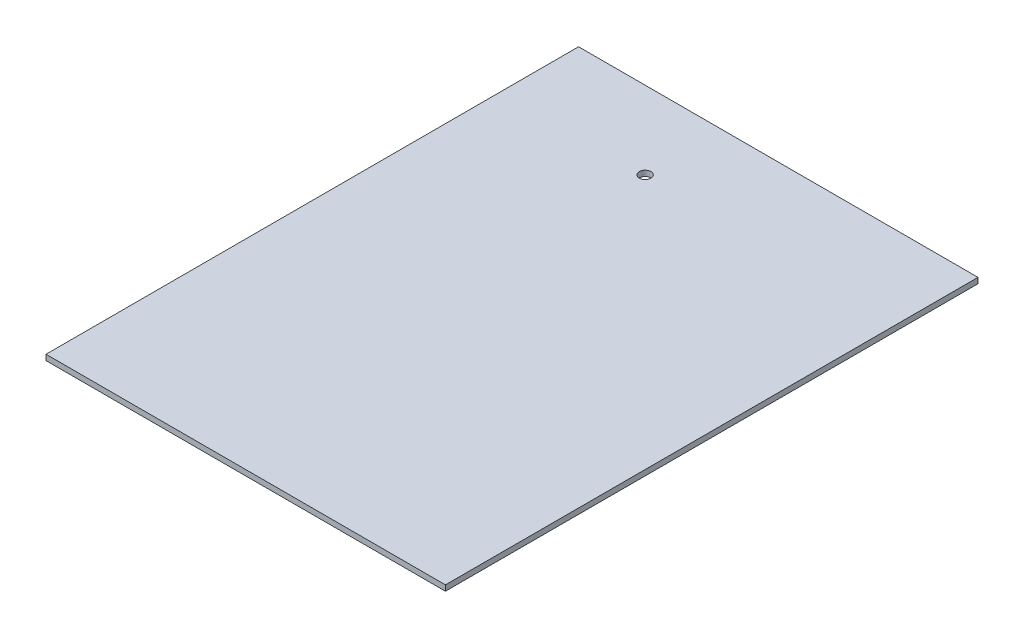
SolidWorks part; units mm, degrees
ref_plane "Front Plane" through (0, 0, 0) normal (0, 0, 1) x (1, 0, 0)
ref_plane "Top Plane" through (0, 0, 0) normal (0, 1, 0) x (1, 0, 0)
ref_plane "Right Plane" through (0, 0, 0) normal (1, 0, 0) x (0, 0, -1)
sketch "Sketch1" plane through (0, 0, 0) normal (0, 1, 0) x (1, 0, 0)
  line L1 (0, 0) -> (-457.2, 0)
  line L2 (0, 0) -> (0, 609.6)
  line L3 (0, 609.6) -> (-457.2, 609.6)
  line L4 (-457.2, 0) -> (-457.2, 609.6)
  dimension "D1" = 457.2
  dimension "D2" = 609.6
extrude "Boss-Extrude1" add sketch "Sketch1" along normal blind 6.35 contours L3 L4 L1 L2
sketch "Sketch2" plane through (0, 6.35, 0) normal (0, 1, 0) x (1, 0, 0)
  line L0 (-310.1815, 609.6) -> (-310.1815, 520.7) construction
  line L1 (0, 609.6) -> (-457.2, 609.6) construction
  line L2 (-292.1, 520.7) -> (-457.2, 520.7) construction
  line L4 (-457.2, 0) -> (-457.2, 609.6) construction
  circle A0 centre (-292.1, 520.7) radius 6.604
  dimension "D1" = 13.208
extrude "Cut-Extrude2" cut sketch "Sketch2" against normal through all contours A0
